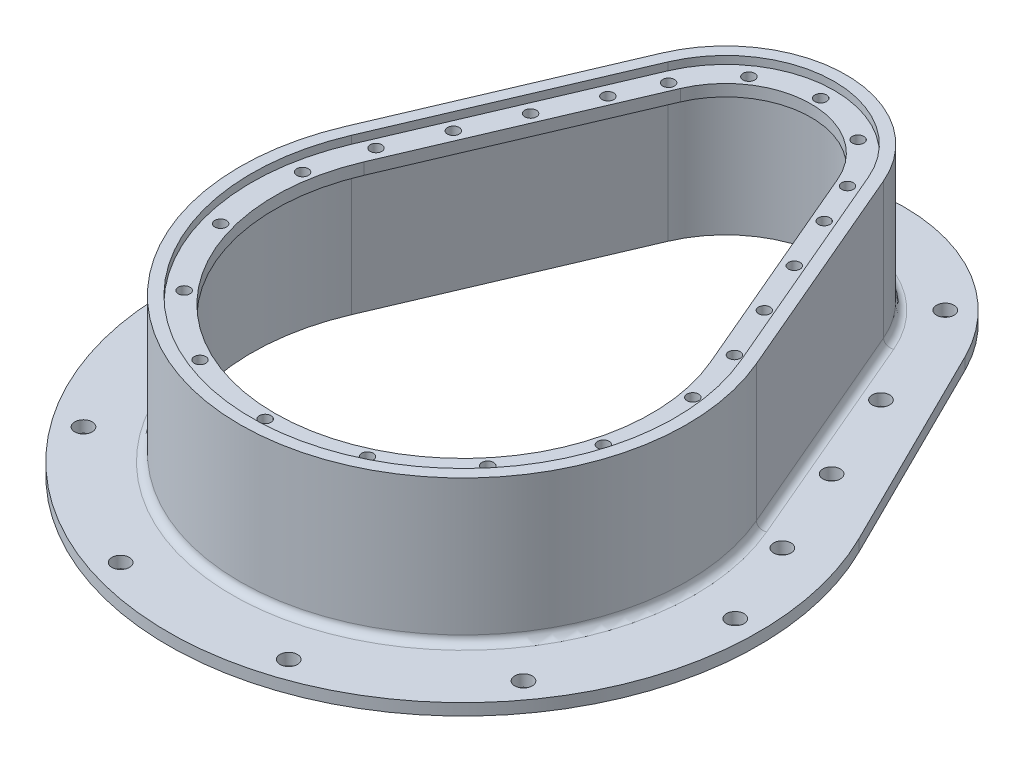
SolidWorks part; units mm, degrees
material "ABS"
ref_plane "Front Plane" through (0, 0, 0) normal (0, 0, 1) x (1, 0, 0)
ref_plane "Top Plane" through (0, 0, 0) normal (0, 1, 0) x (1, 0, 0)
ref_plane "Right Plane" through (0, 0, 0) normal (1, 0, 0) x (0, 0, -1)
sketch "Sketch1" plane through (0, 0, 0) normal (0, 1, 0) x (1, 0, 0)
  line L0 (0, 67.5) -> (0, 0) construction
  line L1 (17.5, -10.1036) -> (0, 20.2073) construction
  line L2 (0, 20.2073) -> (-17.5, -10.1036) construction
  line L3 (-17.5, -10.1036) -> (17.5, -10.1036) construction
  line L4 (44.7903, 89.7222) -> (71.6645, 35.5556) construction
  line L5 (-44.7903, 89.7222) -> (-71.6645, 35.5556) construction
  line L6 (40, 67.5) -> (70, 0) construction
  line L13 (-40, 67.5) -> (-70, 0) construction
  line L19 (-28.5111, 79.6704) -> (-52.8835, 22.5741)
  line L20 (28.5111, 79.6704) -> (52.8835, 22.5741)
  line L21 (-25.7519, 78.4926) -> (-50.1243, 21.3963)
  line L22 (25.7519, 78.4926) -> (50.1243, 21.3963)
  line L23 (41.2071, 87.9444) -> (68.0813, 33.7778)
  line L24 (-41.2071, 87.9444) -> (-68.0813, 33.7778)
  circle A1 centre (0, 0) radius 10.1036 construction
  circle A2 centre (-17.5, -10.1036) radius 1.55 construction
  circle A3 centre (17.5, -10.1036) radius 1.55 construction
  circle A4 centre (0, 20.2073) radius 1.55 construction
  arc A6 (-71.6645, 35.5556) -> (71.6645, 35.5556) centre (0, 0) ccw construction
  arc A8 (44.7903, 89.7222) -> (-44.7903, 89.7222) centre (0, 67.5) ccw construction
  circle A9 centre (0, 0) radius 35 construction
  circle A10 centre (0, 67.5) radius 15 construction
  circle A11 centre (0, 0) radius 45 construction
  circle A12 centre (0, 67.5) radius 22.5 construction
  circle A14 centre (40, 67.5) radius 2.25
  circle A15 centre (70, 0) radius 2.25
  circle A16 centre (56.6312, -41.145) radius 2.25
  circle A17 centre (21.6312, -66.574) radius 2.25
  circle A18 centre (-21.6312, -66.574) radius 2.25
  circle A19 centre (-56.6312, -41.145) radius 2.25
  circle A20 centre (-70, 0) radius 2.25
  circle A21 centre (28.2843, 95.7843) radius 2.25
  circle A22 centre (0, 107.5) radius 2.25
  circle A23 centre (-28.2843, 95.7843) radius 2.25
  circle A24 centre (-40, 67.5) radius 2.25
  circle A25 centre (-50.1535, 44.6547) radius 2.25
  circle A26 centre (-60.3069, 21.8094) radius 2.25
  circle A27 centre (50.1535, 44.6547) radius 2.25
  circle A28 centre (60.3069, 21.8094) radius 2.25
  circle A30 centre (17.8596, -30.1004) radius 2 construction
  circle A31 centre (-23.2495, 26.1622) radius 2 construction
  circle A36 centre (0, 67.5) radius 35 construction
  arc A40 (-52.8835, 22.5741) -> (52.8835, 22.5741) centre (0, 0) ccw
  arc A42 (28.5111, 79.6704) -> (-28.5111, 79.6704) centre (0, 67.5) ccw
  arc A43 (-50.1243, 21.3963) -> (50.1243, 21.3963) centre (0, 0) ccw
  arc A44 (25.7519, 78.4926) -> (-25.7519, 78.4926) centre (0, 67.5) ccw
  arc A45 (-68.0813, 33.7778) -> (68.0813, 33.7778) centre (0, 0) ccw
  arc A46 (41.2071, 87.9444) -> (-41.2071, 87.9444) centre (0, 67.5) ccw
  point P11 (0, 21.0074)
  point P42 (0, 0)
  point P51 (0, 67.5)
  dimension "D3" = 3.1
  dimension "D4" = 4.5
  dimension "D5" = 50
  dimension "D6" = 31
  dimension "D7" = 70
  dimension "D8" = 30
  dimension "D12" = 90
  dimension "D13" = 45
  dimension "D15" = 80
  dimension "D16" = 4.5
  dimension "D22" = 4
  dimension "D23" = 4
  dimension "D24" = 20
  dimension "D32" = 70
  dimension "D9" = 115
  dimension "D2" = 35
  dimension "D10" = 3
  dimension "D11" = 4
  dimension "D17" = 70
  dimension "D25" = 24
  dimension "D20" = 3
  dimension "D21" = 3
  dimension "D18" = 6
  dimension "D19" = 5
extrude "Boss-Extrude1" add sketch "Sketch1" along normal blind 3 contours L23 A46 L24 A45 A14 A15 A16 A17 A18 A19 A20 A21 A22 A23 A24 A25 A26 A27 A28 A42 L20 A40 L19 region at (52.468, 0, -59.7814)
extrude "Boss-Extrude2" add sketch "Sketch1<3>" along normal blind 40 contours L20 A42 L19 A40 A44 L22 A43 L21 region at (0, 0, -96.5619)
sketch "Sketch1<3>" plane through (0, 0, 0) normal (0, 1, 0) x (1, 0, 0) same geometry as "Sketch1"
sketch "Sketch5" plane through (0, 40, 0) normal (0, 1, 0) x (1, 0, 0)
  line L0 (25.7519, 78.4926) -> (50.1243, 21.3963) construction
  line L1 (-25.7519, 78.4926) -> (-50.1243, 21.3963) construction
  line L2 (25.7519, 78.4926) -> (50.1243, 21.3963)
  line L3 (-25.7519, 78.4926) -> (-50.1243, 21.3963)
  line L4 (-20.2337, 76.137) -> (-44.6061, 19.0407)
  line L5 (20.2337, 76.137) -> (44.6061, 19.0407)
  arc A0 (25.7519, 78.4926) -> (-25.7519, 78.4926) centre (0, 67.5) ccw construction
  arc A1 (-50.1243, 21.3963) -> (50.1243, 21.3963) centre (0, 0) ccw construction
  arc A2 (25.7519, 78.4926) -> (-25.7519, 78.4926) centre (0, 67.5) ccw
  arc A3 (-50.1243, 21.3963) -> (50.1243, 21.3963) centre (0, 0) ccw
  arc A4 (20.2337, 76.137) -> (-20.2337, 76.137) centre (0, 67.5) ccw
  arc A5 (-44.6061, 19.0407) -> (44.6061, 19.0407) centre (0, 0) ccw
  dimension "D1" = 6
extrude "Boss-Extrude3" add sketch "Sketch5" against normal blind 3 from offset 2 offset against normal yes
sketch "Sketch6" plane through (0, 38, 0) normal (0, 1, 0) x (1, 0, 0)
  line L0 (0, 67.5) -> (0, 92) construction
  circle A0 centre (0, -51) radius 1.5
  circle A1 centre (0, 92) radius 1.5
  circle A2 centre (14.0526, 87.5692) radius 1.5
  circle A3 centre (23.0225, 75.8795) radius 1.5
  circle A4 centre (21.5535, -46.2217) radius 1.5
  circle A5 centre (39.0683, -32.7822) radius 1.5
  circle A6 centre (49.2622, -13.1998) radius 1.5
  circle A7 centre (50.2252, 8.8561) radius 1.5
  circle A9 centre (27.8353, 65.0559) radius 1.5
  circle A10 centre (33.9352, 51.2573) radius 1.5
  circle A11 centre (40.035, 37.4587) radius 1.5
  circle A12 centre (46.1349, 23.66) radius 1.5
  circle A13 centre (-46.1349, 23.66) radius 1.5
  circle A14 centre (-40.035, 37.4587) radius 1.5
  circle A15 centre (-33.9352, 51.2573) radius 1.5
  circle A16 centre (-27.8353, 65.0559) radius 1.5
  circle A17 centre (-50.2252, 8.8561) radius 1.5
  circle A18 centre (-49.2622, -13.1998) radius 1.5
  circle A19 centre (-39.0683, -32.7822) radius 1.5
  circle A20 centre (-21.5535, -46.2217) radius 1.5
  circle A21 centre (-23.0225, 75.8795) radius 1.5
  circle A22 centre (-14.0526, 87.5692) radius 1.5
  point P11 (0, 67.5)
  point P22 (0, 0)
  dimension "D1" = 3
  dimension "D2" = 3
  dimension "D3" = 51
  dimension "D4" = 92
  dimension "D7" = 3
  dimension "D8" = 4
  dimension "D5" = 3
  dimension "D6" = 5
extrude "Cut-Extrude1" cut sketch "Sketch6" against normal through all
fillet "Fillet1" radius 2 4 edges at (-40.6973, 3, -51.1222) (0, 3, -98.5) (40.6973, 3, -51.1222) (0, 3, 57.5)
